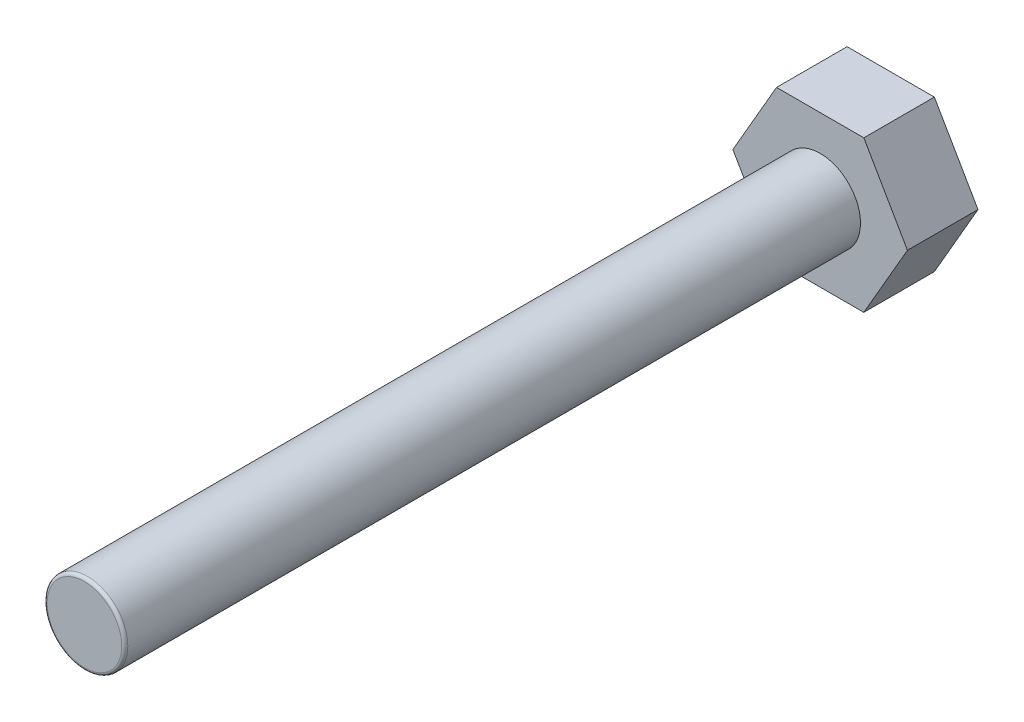
SolidWorks part; units mm, degrees
ref_plane "Alzado" through (0, 0, 0) normal (0, 0, 1) x (1, 0, 0)
ref_plane "Planta" through (0, 0, 0) normal (0, 1, 0) x (1, 0, 0)
ref_plane "Vista lateral" through (0, 0, 0) normal (1, 0, 0) x (0, 0, -1)
sketch "Croquis1" plane through (0, 0, 0) normal (0, 0, 1) x (1, 0, 0)
  line L1 (-4.3301, -7.5) -> (4.3301, -7.5)
  line L2 (4.3301, -7.5) -> (8.6603, 0)
  line L3 (8.6603, 0) -> (4.3301, 7.5)
  line L4 (4.3301, 7.5) -> (-4.3301, 7.5)
  line L5 (-4.3301, 7.5) -> (-8.6603, 0)
  line L6 (-8.6603, 0) -> (-4.3301, -7.5)
  circle A0 centre (0, 0) radius 4
  circle A1 centre (0, 0) radius 7.5 construction
  dimension "D1" = 15
  dimension "D2" = 8
extrude "Saliente-Extruir1" add sketch "Croquis1" along normal blind 80 contours A0
extrude "Saliente-Extruir2" add sketch "Croquis1<3>" along normal blind 7
sketch "Croquis1<3>" plane through (0, 0, 0) normal (0, 0, 1) x (1, 0, 0) same geometry as "Croquis1"
fillet "Redondeo1" radius 0.3 1 edges at (4, 0, 80)
